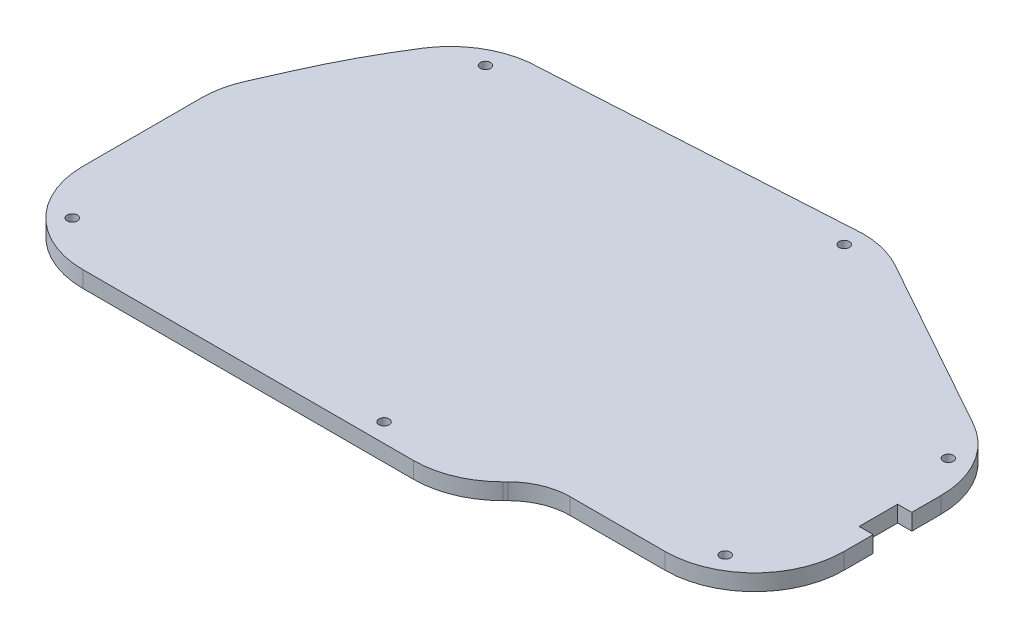
SolidWorks part; units mm, degrees
ref_plane "Front Plane" through (0, 0, 0) normal (0, 0, 1) x (1, 0, 0)
ref_plane "Top Plane" through (0, 0, 0) normal (0, 1, 0) x (1, 0, 0)
ref_plane "Right Plane" through (0, 0, 0) normal (1, 0, 0) x (0, 0, -1)
sketch "Sketch2" plane through (0, 0, 0) normal (0, 1, 0) x (1, 0, 0)
  line L7 (-257.8256, -105.63) -> (-193.4944, -105.63) construction
  line L8 (-181.1201, -100.5044) -> (-180.6101, -99.9944) construction
  line L9 (-172.1248, -96.4797) -> (-153.6496, -96.4797) construction
  line L10 (-136.1496, -78.9797) -> (-136.1496, -60.0821) construction
  line L11 (-145.1341, -44.7936) -> (-179.4485, -25.681) construction
  line L12 (-187.9639, -23.4695) -> (-247.3805, -26.968) construction
  line L13 (-271.0251, -51.648) -> (-273.8196, -57.9411) construction
  line L14 (-275.3256, -65.0434) -> (-275.3256, -88.13) construction
  line L15 (-145.1828, -44.881) -> (-179.4971, -25.7684)
  line L16 (-187.961, -23.5695) -> (-247.3776, -27.068)
  line L17 (-270.9337, -51.6886) -> (-273.7282, -57.9817)
  line L18 (-275.2256, -65.0434) -> (-275.2256, -88.13)
  line L19 (-257.8256, -105.53) -> (-193.4944, -105.53)
  line L20 (-181.1908, -100.4337) -> (-180.6808, -99.9237)
  line L21 (-172.1248, -96.3797) -> (-153.6496, -96.3797)
  line L22 (-136.2496, -78.9797) -> (-136.2496, -73.2809)
  line L23 (-136.2496, -69.5309) -> (-138.9996, -69.5309) construction
  line L24 (-138.9996, -65.7809) -> (-138.9996, -73.2809)
  line L25 (-138.9996, -65.7809) -> (-136.2496, -65.7809)
  line L26 (-138.9996, -73.2809) -> (-136.2496, -73.2809)
  line L27 (-136.2496, -78.9797) -> (-136.2496, -60.0821) construction
  line L28 (-136.2496, -65.7809) -> (-136.2496, -60.0821)
  line L29 (-136.2496, -65.7809) -> (-136.2496, -73.2809) construction
  circle A15 centre (-147.2076, -91.1273) radius 1
  circle A16 centre (-141.795, -53.1155) radius 1
  circle A17 centre (-187.9639, -27.2195) radius 1
  arc A18 (-275.3256, -88.13) -> (-257.8256, -105.63) centre (-257.8256, -88.13) ccw construction
  arc A19 (-193.4944, -105.63) -> (-181.1201, -100.5044) centre (-193.4944, -88.13) ccw construction
  arc A20 (-172.1248, -96.4797) -> (-180.6101, -99.9944) centre (-172.1248, -108.4797) ccw construction
  arc A21 (-153.6496, -96.4797) -> (-136.1496, -78.9797) centre (-153.6496, -78.9797) ccw construction
  arc A22 (-136.1496, -60.0821) -> (-145.1341, -44.7936) centre (-153.6496, -60.0821) ccw construction
  arc A23 (-179.4485, -25.681) -> (-187.9639, -23.4695) centre (-187.9639, -40.9695) ccw construction
  arc A24 (-247.3805, -26.968) -> (-262.1548, -35.0887) centre (-247.3805, -44.468) ccw construction
  arc A25 (-262.1548, -35.0887) -> (-271.0251, -51.648) centre (-154.7153, -103.2964) ccw construction
  arc A26 (-273.8196, -57.9411) -> (-275.3256, -65.0434) centre (-257.8256, -65.0434) ccw construction
  circle A27 centre (-253.0515, -31.942) radius 1
  circle A28 centre (-267.5484, -97.8527) radius 1
  circle A29 centre (-202.8547, -101.88) radius 1
  arc A30 (-179.4971, -25.7684) -> (-187.961, -23.5695) centre (-187.9639, -40.9695) ccw
  arc A31 (-247.3776, -27.068) -> (-262.0703, -35.1423) centre (-247.3805, -44.468) ccw
  arc A32 (-262.0703, -35.1423) -> (-270.9337, -51.6886) centre (-154.7153, -103.2964) ccw
  arc A33 (-273.7282, -57.9817) -> (-275.2256, -65.0434) centre (-257.8256, -65.0434) ccw
  arc A34 (-275.2256, -88.13) -> (-257.8256, -105.53) centre (-257.8256, -88.13) ccw
  arc A35 (-193.4944, -105.53) -> (-181.1908, -100.4337) centre (-193.4944, -88.13) ccw
  arc A36 (-172.1248, -96.3797) -> (-180.6808, -99.9237) centre (-172.1248, -108.4797) ccw
  arc A37 (-153.6496, -96.3797) -> (-136.2496, -78.9797) centre (-153.6496, -78.9797) ccw
  arc A38 (-136.2496, -60.0821) -> (-145.1828, -44.881) centre (-153.6496, -60.0821) ccw
  point P69 (-138.9996, -69.5309)
  dimension "D2" = 7.5
  dimension "D1" = 0.1
extrude "Boss-Extrude1" add sketch "Sketch2" along normal blind 3.175
